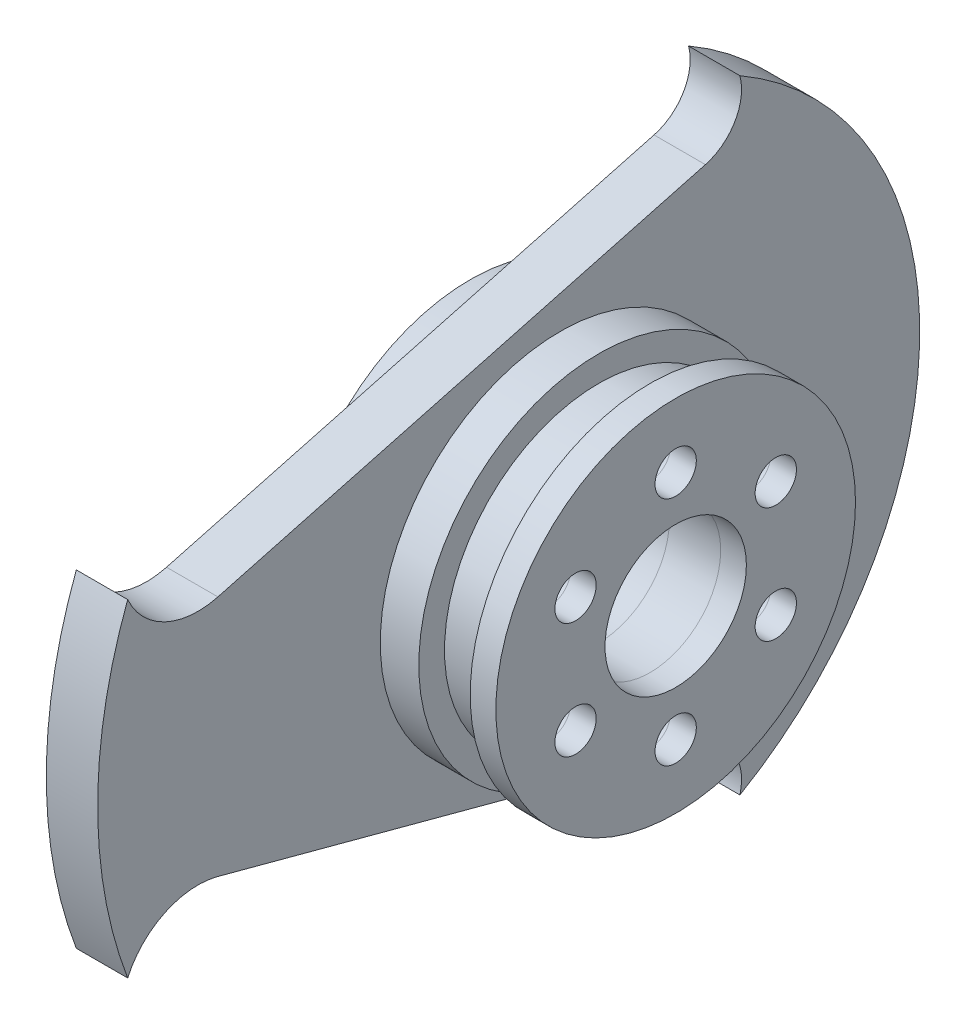
SolidWorks part; units mm, degrees
material "Alum Plate"
ref_plane "Front Plane" through (0, 0, 0) normal (0, 0, 1) x (1, 0, 0)
ref_plane "Top Plane" through (0, 0, 0) normal (0, 1, 0) x (1, 0, 0)
ref_plane "Right Plane" through (0, 0, 0) normal (1, 0, 0) x (0, 0, -1)
other "Center of Mass"
sketch "Sketch3" plane through (0, 0, 0) normal (1, 0, 0) x (0, 0, -1)
  circle A1 centre (0, 0) radius 57.15
  dimension "D1" = 114.3
extrude "Boss-Extrude1" add sketch "Sketch3" along normal mid plane 6.35
sketch "Sketch4" plane through (3.175, 0, 0) normal (1, 0, 0) x (0, 0, -1)
  line L0 (0, 0) -> (0, 14.2875) construction
  line L1 (-4.7625, 0) -> (-4.7625, 14.2875)
  line L2 (4.7625, 0) -> (4.7625, 14.2875)
  arc A0 (-4.7625, 0) -> (4.7625, 0) centre (0, 0) ccw
  arc A1 (4.7625, 14.2875) -> (-4.7625, 14.2875) centre (0, 14.2875) ccw
  point P3 (0, 7.1438)
  point P8 (0, 19.05)
  dimension "D1" = 4.7625
  dimension "D2" = 19.05
extrude "Cut-Extrude1" cut sketch "Sketch4" against normal through all
pattern_circular "CirPattern1" count 6 over 360 about axis through (3.175, 0, 0) along (1, 0, 0) of "Cut-Extrude1"
fillet "Fillet1" radius 2.54 6 edges at (0, 0, 9.525) (0, -8.2489, 4.7625) (0, -8.2489, -4.7625) (0, 0, -9.525) (0, 8.2489, 4.7625) (0, 8.2489, -4.7625)
sketch "Sketch5" plane through (3.175, 0, 0) normal (1, 0, 0) x (0, 0, -1)
  line L12 (-8.5725, 10.4486) -> (-9.9921, 11.2682)
  line L14 (-8.5725, 10.4486) -> (-9.9921, 11.2682)
  line L16 (-4.7625, 14.2875) -> (-4.7625, 12.6483)
  line L18 (-4.7625, 14.2875) -> (-4.7625, 12.6483)
  line L20 (4.7625, 12.6483) -> (4.7625, 14.2875)
  line L22 (4.7625, 12.6483) -> (4.7625, 14.2875)
  line L36 (9.9921, 11.2682) -> (8.5725, 10.4486)
  line L38 (9.9921, 11.2682) -> (8.5725, 10.4486)
  line L40 (13.335, 2.1997) -> (14.7546, 3.0193)
  line L42 (13.335, 2.1997) -> (14.7546, 3.0193)
  line L44 (14.7546, -3.0193) -> (13.335, -2.1997)
  line L46 (14.7546, -3.0193) -> (13.335, -2.1997)
  line L48 (8.5725, -10.4486) -> (9.9921, -11.2682)
  line L49 (8.5725, -10.4486) -> (9.9921, -11.2682)
  line L50 (4.7625, -14.2875) -> (4.7625, -12.6483)
  line L51 (4.7625, -14.2875) -> (4.7625, -12.6483)
  line L52 (-4.7625, -12.6483) -> (-4.7625, -14.2875)
  line L53 (-4.7625, -12.6483) -> (-4.7625, -14.2875)
  line L54 (-9.9921, -11.2682) -> (-8.5725, -10.4486)
  line L55 (-9.9921, -11.2682) -> (-8.5725, -10.4486)
  line L56 (-13.335, -2.1997) -> (-14.7546, -3.0193)
  line L57 (-13.335, -2.1997) -> (-14.7546, -3.0193)
  line L58 (-14.7546, 3.0193) -> (-13.335, 2.1997)
  line L59 (-14.7546, 3.0193) -> (-13.335, 2.1997)
  arc A6 (4.7625, 14.2875) -> (-4.7625, 14.2875) centre (0, 14.2875) ccw
  arc A7 (14.7546, 3.0193) -> (9.9921, 11.2682) centre (12.3733, 7.1438) ccw
  arc A8 (9.9921, -11.2682) -> (14.7546, -3.0193) centre (12.3733, -7.1437) ccw
  arc A9 (-4.7625, -14.2875) -> (4.7625, -14.2875) centre (0, -14.2875) ccw
  arc A10 (-14.7546, -3.0193) -> (-9.9921, -11.2682) centre (-12.3733, -7.1438) ccw
  arc A11 (-9.9921, 11.2682) -> (-14.7546, 3.0193) centre (-12.3733, 7.1437) ccw
  arc A12 (4.7625, 14.2875) -> (-4.7625, 14.2875) centre (0, 14.2875) ccw
  arc A13 (14.7546, 3.0193) -> (9.9921, 11.2682) centre (12.3733, 7.1438) ccw
  arc A14 (9.9921, -11.2682) -> (14.7546, -3.0193) centre (12.3733, -7.1437) ccw
  arc A15 (-4.7625, -14.2875) -> (4.7625, -14.2875) centre (0, -14.2875) ccw
  arc A16 (-14.7546, -3.0193) -> (-9.9921, -11.2682) centre (-12.3733, -7.1438) ccw
  arc A17 (-9.9921, 11.2682) -> (-14.7546, 3.0193) centre (-12.3733, 7.1437) ccw
  arc A24 (-13.335, -2.1997) -> (-13.335, 2.1997) centre (-14.605, 0) ccw
  arc A28 (-13.335, -2.1997) -> (-13.335, 2.1997) centre (-14.605, 0) ccw
  arc A32 (-8.5725, 10.4486) -> (-4.7625, 12.6483) centre (-7.3025, 12.6483) ccw
  arc A36 (-8.5725, 10.4486) -> (-4.7625, 12.6483) centre (-7.3025, 12.6483) ccw
  arc A38 (4.7625, 12.6483) -> (8.5725, 10.4486) centre (7.3025, 12.6483) ccw
  arc A40 (4.7625, 12.6483) -> (8.5725, 10.4486) centre (7.3025, 12.6483) ccw
  arc A42 (13.335, 2.1997) -> (13.335, -2.1997) centre (14.605, 0) ccw
  arc A43 (13.335, 2.1997) -> (13.335, -2.1997) centre (14.605, 0) ccw
  arc A44 (8.5725, -10.4486) -> (4.7625, -12.6483) centre (7.3025, -12.6483) ccw
  arc A45 (8.5725, -10.4486) -> (4.7625, -12.6483) centre (7.3025, -12.6483) ccw
  arc A46 (-4.7625, -12.6483) -> (-8.5725, -10.4486) centre (-7.3025, -12.6483) ccw
  arc A47 (-4.7625, -12.6483) -> (-8.5725, -10.4486) centre (-7.3025, -12.6483) ccw
  dimension "D1" = 0
extrude "Boss-Extrude2" add sketch "Sketch5" against normal up to surface (6.35 mm away) separate body up to face at (-3.175, 0, 0)
sketch "Sketch6" plane through (-3.175, 0, 0) normal (-1, 0, 0) x (0, 0, 1)
  line L0 (0, -22.225) -> (0, -19.05) construction
  circle A0 centre (0, 0) radius 22.225
  arc A1 (-4.7625, -14.2875) -> (4.7625, -14.2875) centre (0, -14.2875) ccw construction
  point P3 (0, -19.05)
  dimension "D1" = 3.175
extrude "Boss-Extrude3" add sketch "Sketch6" along normal blind 4.7625 separate body
mirror "Mirror1" about plane through (0, 0, 0) normal (1, 0, 0) of bodies 105
sketch "Sketch7" plane through (7.9375, 0, 0) normal (1, 0, 0) x (0, 0, -1)
  circle A0 centre (0, 0) radius 19.05
  arc A1 (-9.9921, 11.2682) -> (-14.7546, 3.0193) centre (-12.3733, 7.1437) ccw construction
extrude "Boss-Extrude4" add sketch "Sketch7" along normal blind 6.35 separate body
sketch "Sketch9" plane through (14.2875, 0, 0) normal (1, 0, 0) x (0, 0, -1)
  circle A0 centre (0, 0) radius 22.225 construction
  circle A1 centre (0, 0) radius 22.225
extrude "Boss-Extrude6" add sketch "Sketch9" along normal blind 3.175
sketch "Sketch10" plane through (17.4625, 0, 0) normal (1, 0, 0) x (0, 0, -1)
  line L0 (0, 0) -> (0, 14.2875) construction
  circle A0 centre (0, 0) radius 8.7376
  circle A1 centre (0, 14.2875) radius 2.5527
  arc A2 (4.7625, 14.2875) -> (-4.7625, 14.2875) centre (0, 14.2875) ccw construction
  circle A3 centre (12.3733, 7.1438) radius 2.5527
  circle A4 centre (12.3733, -7.1437) radius 2.5527
  circle A5 centre (0, -14.2875) radius 2.5527
  circle A6 centre (-12.3733, -7.1438) radius 2.5527
  circle A7 centre (-12.3733, 7.1437) radius 2.5527
  point P9 (-0.1809, -16.0097)
  point P10 (0, 0)
  point P20 (0, 0)
  dimension "D1" = 17.4752
  dimension "D2" = 5.1054
  dimension "D3" = 6
extrude "Cut-Extrude2" cut sketch "Sketch10" against normal through all
sketch "Sketch11" plane through (3.175, 0, 0) normal (1, 0, 0) x (0, 0, -1)
  line L0 (-42.2905, 14.9643) -> (17.9605, 31.1085)
  line L1 (-57.15, 0) -> (57.15, 0) construction
  line L2 (44.45, 0) -> (57.15, 0)
  line L3 (0, 0) -> (-53.4408, 20.2536) construction
  line L4 (-53.4408, 20.2536) -> (-44.3198, 0) construction
  line L5 (0, 0) -> (22.225, 38.4948) construction
  line L6 (22.225, 38.4948) -> (32.5397, 0) construction
  arc A0 (-53.4408, 20.2536) -> (-42.2905, 14.9643) centre (-44.7558, 24.1647) ccw
  circle A1 centre (0, 0) radius 57.15 construction
  arc A2 (17.9605, 31.1085) -> (22.225, 38.4948) centre (16.3996, 36.9339) ccw
  arc A3 (22.225, 38.4948) -> (44.45, 0) centre (0, 0) cw
  arc A4 (57.15, 0) -> (-53.4408, 20.2536) centre (0, 0) ccw
  point P10 (27.8263, 34.5986)
  point P17 (16.929, 25.0516)
  point P18 (5.2423, 44.1398)
  point P19 (11.5661, 23.5173)
  point P20 (-49.1246, 10.0895)
  point P21 (23.931, 37.4581)
  point P22 (20.9327, 39.2125)
  point P23 (15.9121, 29.2792)
  dimension "D1" = 9.525
  dimension "D3" = 44.45
  dimension "D5" = 25.4
  dimension "D6" = 15
  dimension "D2" = 45
  dimension "D4" = 45
extrude "Cut-Extrude3" cut sketch "Sketch11" against normal through all
mirror "Mirror2" about plane through (0, 0, 0) normal (0, 1, 0) of "Cut-Extrude3"
